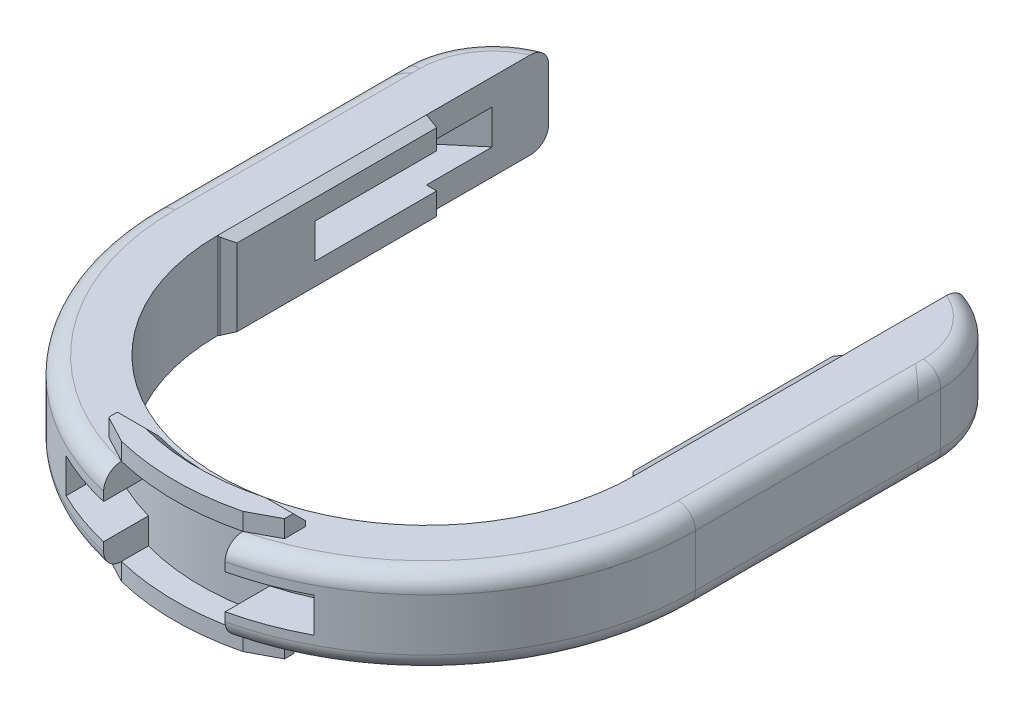
SolidWorks part; units mm, degrees
ref_plane "前视基准面" through (0, 0, 0) normal (0, 0, 1) x (1, 0, 0)
ref_plane "上视基准面" through (0, 0, 0) normal (0, 1, 0) x (1, 0, 0)
ref_plane "右视基准面" through (0, 0, 0) normal (1, 0, 0) x (0, 0, -1)
sketch "草图1" plane through (0, 0, 0) normal (0, 1, 0) x (1, 0, 0)
  circle A0 centre (0, 0) radius 12
  circle A1 centre (0, 0) radius 15.5
  circle A2 centre (0, 0) radius 13
  circle A3 centre (0, 0) radius 14.5
  dimension "D1" = 24
  dimension "D2" = 31
  dimension "D3" = 26
  dimension "D4" = 29
extrude "凸台-拉伸1" add sketch "草图1" along normal mid plane 2 contours A2 A0 | A1 A3 region at (-15.0616, 0, 0) region at (-12.6323, 0, 0)
sketch "草图2" plane through (0, 1, 0) normal (0, 1, 0) x (1, 0, 0)
  circle A0 centre (0, 0) radius 15.5
  circle A1 centre (0, 0) radius 12
extrude "凸台-拉伸2" add sketch "草图2" along normal blind 1.5
sketch "草图3" plane through (0, -1, 0) normal (0, -1, 0) x (1, 0, 0)
  circle A0 centre (0, 0) radius 15.5
  circle A1 centre (0, 0) radius 12
extrude "凸台-拉伸3" add sketch "草图3" along normal blind 1.5
fillet "圆角1" radius 1 2 edges at (0, 2.5, 15.5) (0, -2.5, -15.5)
sketch "草图4" plane through (0, -2.5, 0) normal (0, -1, 0) x (1, 0, 0)
  line L0 (-20.1915, 0) -> (23.3929, 0)
  line L1 (23.3929, 0) -> (23.3929, -19.2021)
  line L2 (23.3929, -19.2021) -> (-20.1915, -19.2021)
  line L3 (-20.1915, -19.2021) -> (-20.1915, 0)
extrude "切除-拉伸1" cut sketch "草图4" against normal blind 14.5
sketch "草图5" plane through (0, 0, 0) normal (0, 0, -1) x (-1, 0, 0)
  line L0 (-14.5, -1) -> (-13, -1) construction
  line L1 (-13, -1) -> (-13, 1) construction
  line L2 (-14.5, -1) -> (-14.5, 1) construction
  line L3 (-13, 1) -> (-14.5, 1) construction
  line L4 (-14.5, -2.5) -> (-12, -2.5) construction
  line L5 (-12, -2.5) -> (-12, 2.5) construction
  line L6 (-15.5, -1.5) -> (-15.5, 1.5) construction
  line L7 (-12, 2.5) -> (-14.5, 2.5) construction
  line L8 (-14.5, -1) -> (-13, -1)
  line L9 (-13, -1) -> (-13, 1)
  line L10 (-14.5, -1) -> (-14.5, 1)
  line L11 (-13, 1) -> (-14.5, 1)
  line L12 (-14.5, -2.5) -> (-12, -2.5)
  line L13 (-12, -2.5) -> (-12, 2.5)
  line L14 (-15.5, -1.5) -> (-15.5, 1.5)
  line L15 (-12, 2.5) -> (-14.5, 2.5)
  line L16 (12, -2.5) -> (14.5, -2.5) construction
  line L17 (15.5, 1.5) -> (15.5, -1.5) construction
  line L18 (14.5, 2.5) -> (12, 2.5) construction
  line L19 (12, 2.5) -> (12, -2.5) construction
  line L20 (13, -1) -> (14.5, -1) construction
  line L21 (14.5, 1) -> (14.5, -1) construction
  line L22 (13, 1) -> (13, -1) construction
  line L23 (14.5, 1) -> (13, 1) construction
  line L24 (12, -2.5) -> (14.5, -2.5)
  line L25 (15.5, 1.5) -> (15.5, -1.5)
  line L26 (14.5, 2.5) -> (12, 2.5)
  line L27 (12, 2.5) -> (12, -2.5)
  line L28 (13, -1) -> (14.5, -1)
  line L29 (14.5, 1) -> (14.5, -1)
  line L30 (13, 1) -> (13, -1)
  line L31 (14.5, 1) -> (13, 1)
  arc A0 (-15.5, -1.5) -> (-14.5, -2.5) centre (-14.5, -1.5) ccw construction
  arc A1 (-14.5, 2.5) -> (-15.5, 1.5) centre (-14.5, 1.5) ccw construction
  arc A2 (-15.5, -1.5) -> (-14.5, -2.5) centre (-14.5, -1.5) ccw
  arc A3 (-14.5, 2.5) -> (-15.5, 1.5) centre (-14.5, 1.5) ccw
  arc A4 (14.5, -2.5) -> (15.5, -1.5) centre (14.5, -1.5) ccw construction
  arc A5 (15.5, 1.5) -> (14.5, 2.5) centre (14.5, 1.5) ccw construction
  arc A6 (14.5, -2.5) -> (15.5, -1.5) centre (14.5, -1.5) ccw
  arc A7 (15.5, 1.5) -> (14.5, 2.5) centre (14.5, 1.5) ccw
extrude "凸台-拉伸4" add sketch "草图5" along normal blind 23
sketch "草图7" plane through (0, 0, 0) normal (0, 0, 1) x (1, 0, 0)
  line L0 (12, 2.5) -> (11.407, 2.1553)
  line L1 (11.407, 2.1553) -> (11.407, -2.2744)
  line L2 (11.407, -2.2744) -> (12, -2.5)
  line L3 (12, -2.5) -> (12, 2.5)
  line L4 (0, 6.6059) -> (0, -7.3859) construction
  line L5 (-12, -2.5) -> (-12, 2.5)
  line L6 (-11.407, -2.2744) -> (-12, -2.5)
  line L7 (-11.407, 2.1553) -> (-11.407, -2.2744)
  line L8 (-12, 2.5) -> (-11.407, 2.1553)
extrude "凸台-拉伸5" add sketch "草图7" against normal blind 12
chamfer "倒角3" distance 0.5 angle 45 2 edges at (-11.407, -0.0596, 0) (11.407, -0.0596, 0)
sketch "草图6" plane through (0, 0, -23) normal (0, 0, -1) x (-1, 0, 0)
  line L1 (14.5, -1) -> (-14.5, -1)
  line L2 (14.5, -1) -> (14.5, 1)
  line L3 (14.5, 1) -> (-14.5, 1)
  line L4 (-14.5, -1) -> (-14.5, 1)
  line L5 (14.5, -1) -> (-14.5, 1) construction
  line L6 (14.5, 1) -> (-14.5, -1) construction
  point P0 (0, 0)
extrude "切除-拉伸2" cut sketch "草图6" against normal blind 18
sketch "草图9" plane through (0, 2.5, 0) normal (0, 1, 0) x (1, 0, 0)
  line L0 (-9.3964, 22.8567) -> (-17.3685, 11.1822)
  line L1 (-17.3685, 11.1822) -> (-17.3685, 24.0192)
  line L2 (-17.3685, 24.0192) -> (-9.3964, 22.8567)
  line L3 (0, 32.954) -> (0, -20.5545) construction
  line L4 (17.3685, 24.0192) -> (9.3964, 22.8567)
  line L5 (17.3685, 11.1822) -> (17.3685, 24.0192)
  line L6 (9.3964, 22.8567) -> (17.3685, 11.1822)
  point P9 (-17.3685, 13.7621)
extrude "切除-拉伸3" cut sketch "草图9" against normal blind 12
sketch "草图10" plane through (0, 0, 0) normal (0, 1, 0) x (1, 0, 0)
  line L2 (0, 30.988) -> (0, -29.4679) construction
  line L5 (12, 19.0439) -> (12, 15.7913)
  line L6 (12, 19.0439) -> (12, 12) construction
  line L7 (12, 15.7913) -> (15.5, 12.8395)
  line L8 (15.5, 13.9184) -> (15.5, 0) construction
  line L10 (-12, 19.0439) -> (-12, 15.7913)
  line L11 (-12, 15.7913) -> (-15.5, 12.8395)
  line L12 (15.5, 14.1271) -> (15.5, 12.8395)
  line L13 (-15.5, 14.1271) -> (-15.5, 12.8395)
  arc A0 (15.5, 14.1271) -> (12, 19.0439) centre (10.2965, 14.1271) ccw
  arc A1 (-15.5, 14.1271) -> (-12, 19.0439) centre (-10.2965, 14.1271) cw
  point P1 (15.5, 12.8395)
  point P21 (12, 15.7913)
extrude "凸台-拉伸6" add sketch "草图10" along normal mid plane 5
fillet "圆角2" radius 1 8 edges at (14.5356, 2.5, -17.1448) (-14.5356, -2.5, -17.1448) (-14.5356, 2.5, -17.1448) (14.5356, -2.5, -17.1448) (-15.5, -2.5, -13.4833) (-15.5, 2.5, -13.4833) (15.5, -2.5, -13.4833) (15.5, 2.5, -13.4833)
sketch "草图11" plane through (0, 0, 0) normal (0, 1, 0) x (1, 0, 0)
  line L1 (3.5, -18.8834) -> (-3.5, -18.8834)
  line L2 (3.5, -18.8834) -> (3.5, -12.52)
  line L4 (-3.5, -18.8834) -> (-3.5, -12.52)
  line L5 (3.5, -18.8834) -> (-3.1701, -12.6076) construction
  line L6 (3.1701, -12.6076) -> (-3.5, -18.8834) construction
  arc A0 (-13, 0) -> (13, 0) centre (0, 0) ccw construction
  arc A1 (-3.5, -12.52) -> (3.5, -12.52) centre (0, 0) ccw
  point P0 (0, -15.5903)
  dimension "D1" = 7
extrude "切除-拉伸4" cut sketch "草图11" against normal mid plane 5
sketch "草图12" plane through (0, 2.5, 0) normal (0, 1, 0) x (1, 0, 0)
  line L4 (-3.5, -14.0712) -> (-5.0638, -13.2401)
  line L5 (-5.0638, -13.2401) -> (-5.0638, -12.0384)
  line L7 (-3.3654, -12.0384) -> (-5.0638, -12.0384)
  line L8 (3.5, -14.0712) -> (5.0638, -13.2401)
  line L9 (5.0638, -13.2401) -> (5.0638, -12.0384)
  line L10 (3.3654, -12.0384) -> (5.0638, -12.0384)
  arc A2 (-3.5, -14.0712) -> (3.5, -14.0712) centre (0, 0) ccw
  arc A3 (-3.3654, -12.0384) -> (3.3654, -12.0384) centre (0, 0) ccw
  point P12 (0, -8.0379)
extrude "凸台-拉伸7" add sketch "草图12" along normal blind 1 contours A2 L8 L9 L10 A3 L7 L5 L4
chamfer "倒角4" distance 0.7 angle 45 3 edges at (4.2146, 3.5, 12.0384) (-4.2146, 3.5, 12.0384) (0, 3.5, 12.5)
mirror "镜向1" about plane through (0, 0, 0) normal (0, 1, 0) of "倒角4", "凸台-拉伸7"
sketch "草图13" plane through (0, 0, 0) normal (0, 1, 0) x (1, 0, 0)
  line L0 (-6.8683, -11.8898) -> (-2.6278, -13.5112)
  line L1 (-2.6278, -13.5112) -> (4.1069, -13.137)
  line L2 (4.1069, -13.137) -> (7.2249, -11.8898)
  line L3 (7.2249, -11.8898) -> (7.2249, -16.4109)
  line L4 (7.2249, -16.4109) -> (-6.8683, -16.4109)
  line L5 (-6.8683, -16.4109) -> (-6.8683, -11.8898)
extrude "切除-拉伸5" cut sketch "草图13" against normal mid plane 2
